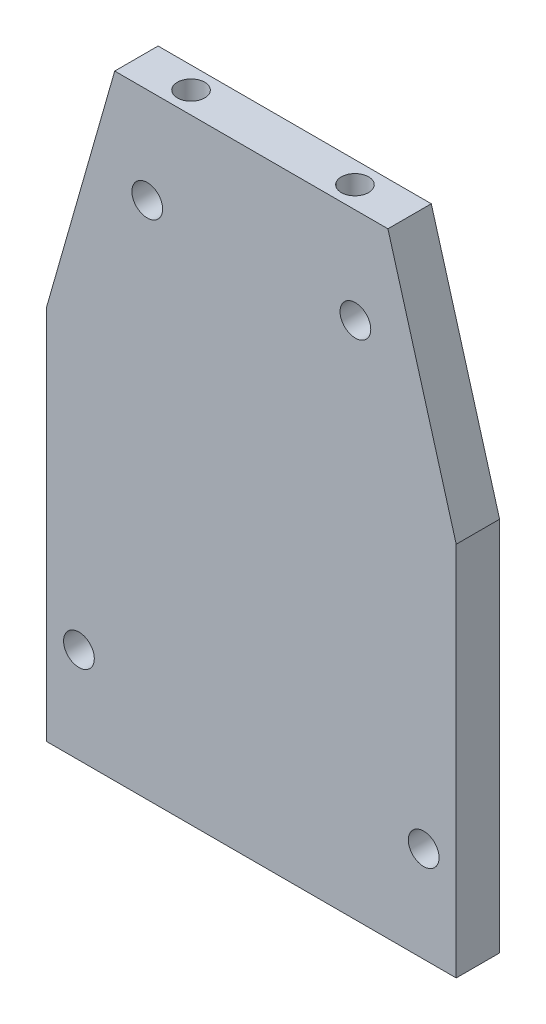
SolidWorks part; units mm, degrees
material "6061 Alloy"
ref_plane "Front Plane" through (0, 0, 0) normal (0, 0, 1) x (1, 0, 0)
ref_plane "Top Plane" through (0, 0, 0) normal (0, 1, 0) x (1, 0, 0)
ref_plane "Right Plane" through (0, 0, 0) normal (1, 0, 0) x (0, 0, -1)
sketch "Sketch1" plane through (0, 0, 0) normal (0, 0, 1) x (1, 0, 0)
  line L0 (-20, 45) -> (20, 45)
  line L5 (-30, -45) -> (30, -45)
  line L6 (0, 45) -> (0, -45) construction
  line L7 (-20, 45) -> (-30, 10)
  line L8 (-30, 10) -> (-30, -45)
  line L9 (30, 10) -> (30, -45)
  line L10 (20, 45) -> (30, 10)
  dimension "D1" = 90
  dimension "D2" = 60
  dimension "D3" = 40
  dimension "D4" = 55
extrude "1/4" add sketch "Sketch1" along normal mid plane 6.35
sketch "Sketch4" plane through (0, 45, 0) normal (0, 1, 0) x (1, 0, 0)
  line L0 (0, -3.175) -> (0, 3.175) construction
  line L1 (0, 0) -> (-12, 0) construction
  line L2 (20, -3.175) -> (-20, -3.175) construction
  line L3 (20, 3.175) -> (-20, 3.175) construction
  circle A0 centre (-12, 0) radius 2
  circle A1 centre (12, 0) radius 2
  dimension "D2" = 4
  dimension "D1" = 12
extrude "M4_DRILL" cut sketch "Sketch4" against normal blind 8
sketch "Sketch5" plane through (0, -45, 0) normal (0, -1, 0) x (-1, 0, 0)
  line L0 (0, -3.175) -> (0, 3.175) construction
  line L2 (0, 0) -> (-20, 0) construction
  line L3 (30, -3.175) -> (-30, -3.175) construction
  line L4 (30, 3.175) -> (-30, 3.175) construction
  circle A0 centre (-20, 0) radius 2
  circle A1 centre (20, 0) radius 2
  circle A2 centre (0, 0) radius 2
  dimension "D1" = 4
  dimension "D2" = 20
extrude "M4_DRILL2" cut sketch "Sketch5" against normal blind 8
sketch "Sketch6" plane through (0, 0, 3.175) normal (0, 0, 1) x (1, 0, 0)
  line L0 (-30, -45) -> (30, -45) construction
  line L1 (-30, 10) -> (-30, -45) construction
  line L2 (0, 0) -> (0, -17.9243) construction
  line L3 (20, 45) -> (-20, 45) construction
  circle A0 centre (-25.2375, -31) radius 2.25
  circle A1 centre (25.2375, -31) radius 2.25
  circle A2 centre (-15.2375, 31) radius 2.25
  circle A3 centre (15.2375, 31) radius 2.25
  dimension "D1" = 4.5
  dimension "D6" = 4.5
  dimension "D2" = 14
  dimension "D3" = 4.7625
  dimension "D4" = 14
  dimension "D5" = 4.7625
extrude "M4_through" cut sketch "Sketch6" against normal up to surface (6.35 mm away) up to face at (0, 3.3333, -3.175)
